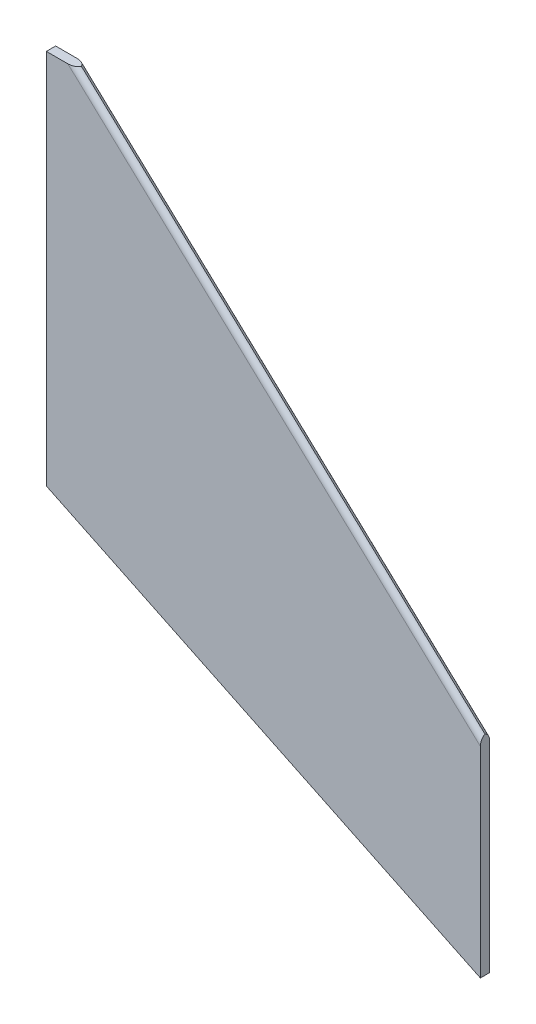
SolidWorks part; units mm, degrees
ref_plane "Front Plane" through (0, 0, 0) normal (0, 0, 1) x (1, 0, 0)
ref_plane "Top Plane" through (0, 0, 0) normal (0, 1, 0) x (1, 0, 0)
ref_plane "Right Plane" through (0, 0, 0) normal (1, 0, 0) x (0, 0, -1)
sketch "Sketch2" plane through (0, 0, 0) normal (0, 0, 1) x (1, 0, 0)
  line L0 (-24.1651, -826.2898) -> (140.9309, -980.2949)
  line L1 (140.9309, -980.2949) -> (140.9309, -1065.8703)
  line L2 (140.9309, -1065.8703) -> (-36.6948, -980.2949)
  line L3 (-36.6948, -980.2949) -> (-36.6948, -826.2898)
  line L4 (-24.1651, -826.2898) -> (-36.6948, -826.2898)
extrude "Boss-Extrude1" add sketch "Sketch2" along normal blind 3.81
fillet "Fillet1" radius 2.54 2 edges at (58.3829, -903.2924, 3.81) (58.3829, -903.2924, 0)
